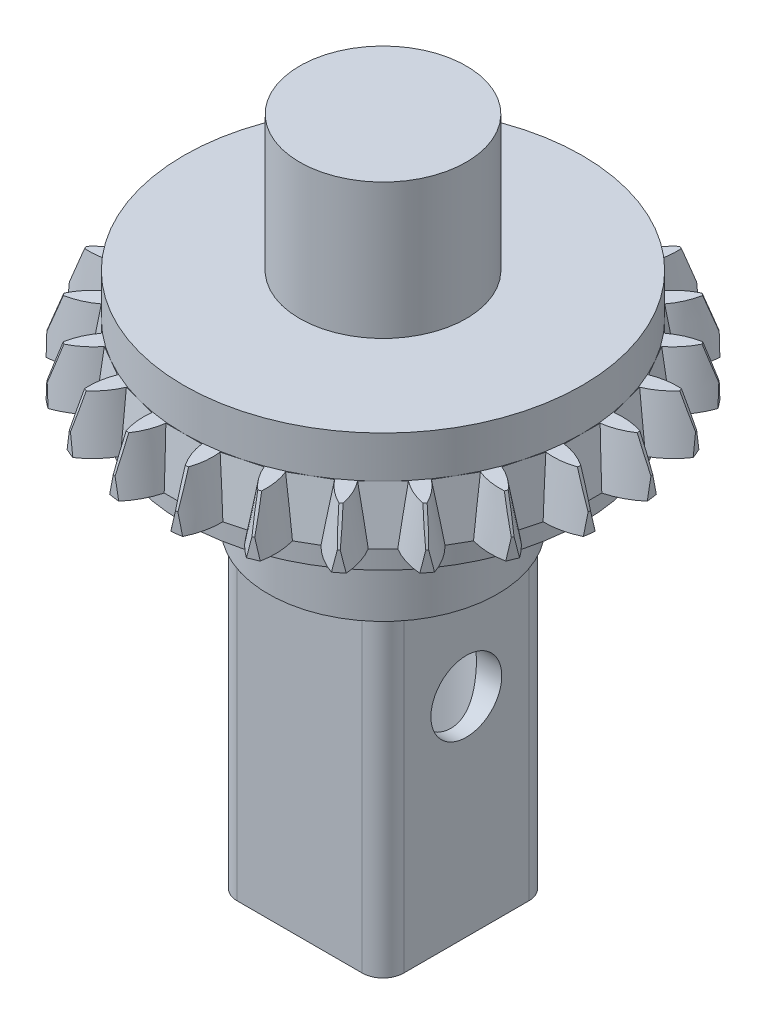
SolidWorks part; units mm, degrees
ref_plane "Front Plane" through (0, 0, 0) normal (0, 0, 1) x (1, 0, 0)
ref_plane "Top Plane" through (0, 0, 0) normal (0, 1, 0) x (1, 0, 0)
ref_plane "Right Plane" through (0, 0, 0) normal (1, 0, 0) x (0, 0, -1)
sketch "Sketch1" plane through (0, 0, 0) normal (0, 1, 0) x (1, 0, 0)
  circle A0 centre (0, 0) radius 11.5
  dimension "D1" = 23
extrude "Boss-Extrude1" add sketch "Sketch1" along normal blind 2.5 contours A0
sketch "Sketch4" plane through (0, 0, 0) normal (0, -1, 0) x (1, 0, 0)
  line L0 (0, 0) -> (0, 12) construction
  line L2 (-0.5, 10) -> (0.5, 10)
  arc A0 (0.5, 10) -> (1.25, 11.4319) centre (3.8916, 9.1358) cw
  arc A1 (-0.5, 10) -> (-1.25, 11.4319) centre (-3.8916, 9.1358) ccw
  arc A2 (-1.25, 11.4319) -> (1.25, 11.4319) centre (0, 0) cw
  circle A3 centre (0, 0) radius 11.5 construction
  point P8 (0, 10)
  dimension "D3" = 3.5
  dimension "D5" = 2
  dimension "D1" = 2.5
  dimension "D2" = 1
  dimension "D4" = 12
extrude "Cut-Extrude2" cut sketch "Sketch4" against normal up to surface (2.5 mm away) draft 10
pattern_circular "CirPattern1" count 24 over 360 about axis through (0, 0, 0) along (0, 1, 0) of "Cut-Extrude2"
sketch "Sketch9" plane through (0, 0, 0) normal (0, 0, 1) x (1, 0, 0)
  line L0 (11.75, 0.25) -> (11.75, 2.5)
  line L1 (11.75, 2.5) -> (10.9311, 2.5)
  line L2 (10.9311, 2.5) -> (11.75, 0.25)
  line L4 (0, 0) -> (0, 13.1477) construction
  line L6 (1.6647, 2.5) -> (1.4444, 2.5) construction
  dimension "D1" = 2.25
  dimension "D2" = 20
  dimension "D3" = 23.5
revolve "Cut-Revolve1" cut sketch "Sketch9" angle 360 about L4
sketch "Sketch5" plane through (0, 2.5, 0) normal (0, 1, 0) x (1, 0, 0)
  circle A0 centre (0, 0) radius 4
  dimension "D1" = 8
extrude "Boss-Extrude2" add sketch "Sketch5" along normal blind 8.5
sketch "Sketch7" plane through (0, 0, 0) normal (0, -1, 0) x (1, 0, 0)
  line L0 (0.8619, -9.5592) -> (-0.8619, -9.5592) construction
  line L1 (0.8619, -9.5592) -> (-0.8619, -9.5592) construction
  circle A0 centre (0, 0) radius 9.5592
extrude "Boss-Extrude4" add sketch "Sketch7" along normal blind 1.2
sketch "Sketch10" plane through (0, 2.5, 0) normal (0, 1, 0) x (1, 0, 0)
  circle A0 centre (0, 0) radius 9.5592 construction
  circle A1 centre (0, 0) radius 9.5592
extrude "Boss-Extrude5" add sketch "Sketch10" along normal blind 2
sketch "Sketch11" plane through (0, -1.2, 0) normal (0, -1, 0) x (1, 0, 0)
  circle A0 centre (0, 0) radius 5.5
  dimension "D1" = 11
extrude "Boss-Extrude6" add sketch "Sketch11" along normal blind 5
sketch "Sketch6" plane through (0, -6.2, 0) normal (0, -1, 0) x (1, 0, 0)
  line L1 (-4, -4) -> (4, -4)
  line L2 (-4, -4) -> (-4, 4)
  line L3 (-4, 4) -> (4, 4)
  line L4 (4, -4) -> (4, 4)
  line L5 (-4, -4) -> (4, 4) construction
  line L6 (-4, 4) -> (4, -4) construction
  circle A0 centre (0, 0) radius 3.26
  dimension "D2" = 6.52
  dimension "D1" = 8
extrude "Boss-Extrude3" add sketch "Sketch6" along normal blind 15
sketch "Sketch8" plane through (-4, 0, 0) normal (-1, 0, 0) x (0, 0, 1)
  line L0 (0, -21.2) -> (0, 0) construction
  line L1 (4, -21.2) -> (-4, -21.2) construction
  line L2 (4, -6.2) -> (3.7749, -6.2) construction
  circle A0 centre (0, -11.2) radius 1.7
  dimension "D1" = 5
  dimension "D2" = 3.4
extrude "Cut-Extrude3" cut sketch "Sketch8" against normal through all
fillet "Fillet1" radius 1 4 edges at (-4, -13.7, 4) (4, -13.7, 4) (4, -13.7, -4) (-4, -13.7, -4)
fillet "Fillet2" [suppressed] radius 1
